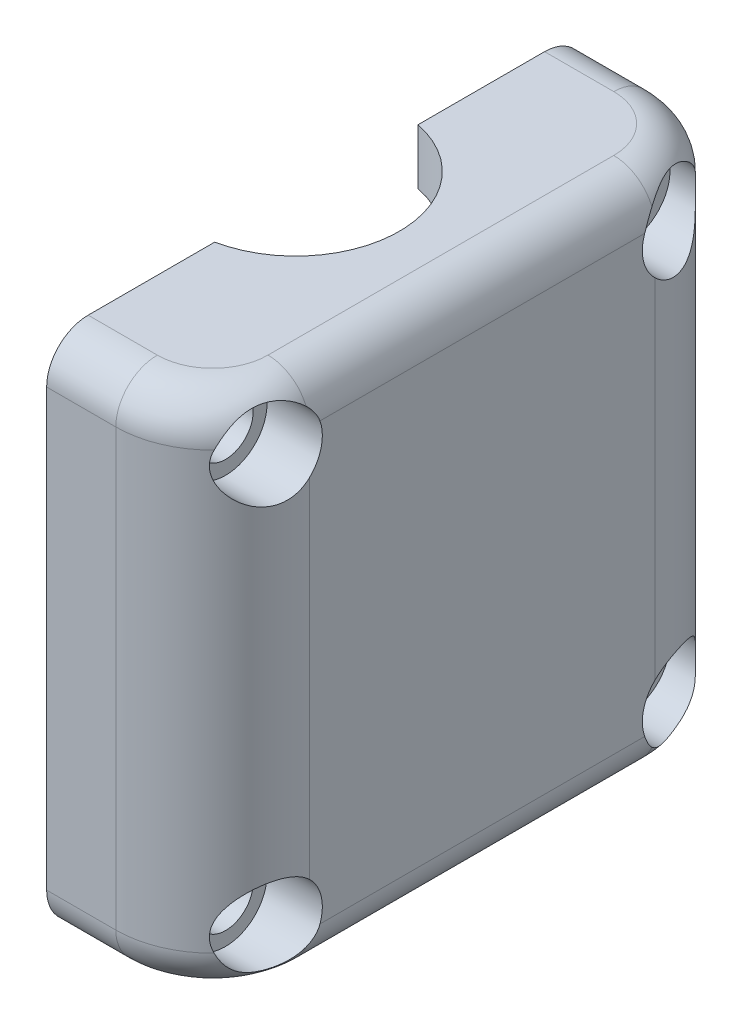
SolidWorks part; units mm, degrees
ref_plane "Plan de face" through (0, 0, 0) normal (0, 0, 1) x (1, 0, 0)
ref_plane "Plan de dessus" through (0, 0, 0) normal (0, 1, 0) x (1, 0, 0)
ref_plane "Plan de droite" through (0, 0, 0) normal (1, 0, 0) x (0, 0, -1)
sketch "Esquisse1" plane through (0, 0, 0) normal (0, 1, 0) x (1, 0, 0)
  line L0 (0, 18.2074) -> (0, 19.5) construction
  line L1 (0, 0) -> (12, 0) construction
  line L2 (0, 0) -> (0, 39) construction
  line L3 (0, 39) -> (12, 39) construction
  line L4 (12, 0) -> (12, 39) construction
  line L5 (0, 19.5) -> (-1.5, 19.5) construction
  line L6 (0, 29.1339) -> (0, 39)
  line L7 (0, 39) -> (12, 39)
  line L8 (12, 39) -> (12, 0)
  line L9 (12, 0) -> (0, 0)
  line L10 (0, 0) -> (0, 9.8661)
  circle A0 centre (-1.5, 19.5) radius 9.75 construction
  arc A1 (0, 29.1339) -> (0, 9.8661) centre (-1.5, 19.5) cw
  dimension "D4" = 19.5
  dimension "D1" = 39
  dimension "D2" = 12
  dimension "D3" = 1.5
extrude "Boss.-Extru.1" add sketch "Esquisse1" along normal blind 37.5
sketch "Esquisse2" plane through (0, 0, 0) normal (0, -1, 0) x (1, 0, 0)
  line L0 (0, 0) -> (0, -39) construction
  line L1 (0, -19.5) -> (-1.5, -19.5) construction
  line L2 (0, -12.1515) -> (0, 0) construction
  line L3 (0, 0) -> (12, 0)
  line L4 (12, 0) -> (12, -39)
  line L5 (12, -39) -> (0, -39)
  line L6 (0, -39) -> (0, -26.8485) construction
  line L7 (0, -26.8485) -> (0, -39)
  line L8 (0, 0) -> (0, -12.1515)
  circle A0 centre (-1.5, -19.5) radius 7.5 construction
  arc A1 (0, -12.1515) -> (0, -26.8485) centre (-1.5, -19.5) cw
  dimension "D2" = 15
  dimension "D1" = 1.5
extrude "Boss.-Extru.2" add sketch "Esquisse2" against normal blind 4
ref_plane "Plan1" through (0, 18.75, 0) normal (0, 1, 0) x (1, 0, 0)
mirror "Symétrie1" about plane through (0, 18.75, 0) normal (0, 1, 0) of "Boss.-Extru.2"
sketch "Esquisse3" plane through (0, 0, 0) normal (-1, 0, 0) x (0, 0, 1)
  line L0 (-29.1339, 33.5) -> (-39, 33.5) construction
  line L1 (-39, 37.5) -> (-39, 0) construction
  line L2 (-19.5, 37.5) -> (-19.5, 0) construction
  line L3 (-12.1515, 37.5) -> (-26.8485, 37.5) construction
  line L4 (-26.8485, 0) -> (-12.1515, 0) construction
  line L5 (-39, 18.75) -> (0, 18.75) construction
  line L6 (0, 37.5) -> (0, 0) construction
  circle A0 centre (-34.067, 33.5) radius 2
  circle A1 centre (-34.067, 4) radius 2
  circle A2 centre (-4.933, 4) radius 2
  circle A3 centre (-4.933, 33.5) radius 2
  dimension "D1" = 4
extrude "Enlèv. mat.-Extru.1" cut sketch "Esquisse3" against normal through all
sketch "Esquisse5" plane through (12, 0, 0) normal (1, 0, 0) x (0, 0, -1)
  circle A0 centre (4.933, 33.5) radius 3
  circle A1 centre (34.067, 33.5) radius 3
  circle A2 centre (34.067, 4) radius 3
  circle A3 centre (4.933, 4) radius 3
  dimension "D1" = 6
extrude "Enlèv. mat.-Extru.2" cut sketch "Esquisse5" against normal blind 4
fillet "Congé1" radius 7 2 edges at (12, 18.75, -39) (12, 18.75, 0)
fillet "Congé2" radius 3 10 edges at (2.5, 0, 0) (9.9497, 0, -2.0503) (2.5, 0, -39) (9.9497, 0, -36.9497) (2.5, 37.5, 0) (9.9497, 37.5, -2.0503) (2.5, 37.5, -39) (9.9497, 37.5, -36.9497) (12, 0, -19.5) (12, 37.5, -19.5)
